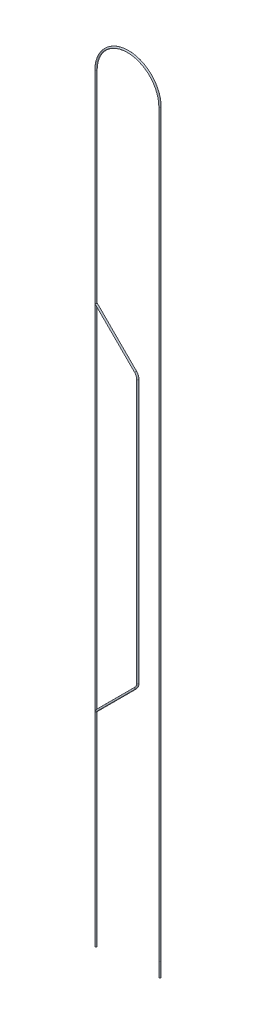
SolidWorks part; units mm, degrees
ref_plane "Plano frontal" through (0, 0, 0) normal (0, 0, 1) x (1, 0, 0)
ref_plane "Plano superior" through (0, 0, 0) normal (0, 1, 0) x (1, 0, 0)
ref_plane "Plano direito" through (0, 0, 0) normal (1, 0, 0) x (0, 0, -1)
sketch3d "3DSketch2"
  line L0 (-21588.0788, -1707.0358, 40468.4738) -> (-21588.0788, -1707.0358, 40492.9638) construction
  line L1 (-21551.0788, -1707.0358, 40468.4738) -> (-21551.0788, -1707.0358, 40480.4738) construction
  line L2 (-21551.0788, -1707.0358, 40468.4738) -> (-21625.0788, -1707.0358, 40468.4738) construction
  line L3 (-21625.0788, -1707.0358, 40468.4738) -> (-21625.0788, -1707.0358, 40480.4738) construction
  line L4 (-21551.0788, -1707.0358, 40480.4738) -> (-21625.0788, -1707.0358, 40480.4738) construction
  line L5 (-21588.0788, -1707.0358, 40492.9638) -> (-21588.0788, -1687.1987, 40492.9638) construction
  line L6 (-21588.0788, -1687.1987, 40492.9638) -> (-21618.6093, -1687.1987, 40492.9638) construction
  line L7 (-21588.0788, -1707.0358, 40492.9638) -> (-21588.0788, 11679.1105, 40492.9638)
  line L8 (-21588.0788, 11679.1105, 40492.9638) -> (-22746.0788, 11679.1105, 40492.9638) construction
  line L9 (-22746.0788, 11679.1105, 40492.9638) -> (-22746.0788, -1710.0519, 40492.9638)
  line L10 (-22167.0788, 11679.1105, 40492.9638) -> (-22167.0788, 12258.1105, 40492.9638) construction
  line L11 (-22746.0788, -1710.0519, 40492.9638) -> (-22746.0788, -2059.4505, 40492.9638)
  line L12 (-21588.0788, -1707.0358, 40492.9638) -> (-21588.0788, -1963.807, 40492.9638)
  line L13 (-22746.0788, -1710.0519, 40492.9638) -> (-21588.0788, -1710.0519, 40492.9638) construction
  circle A0 centre (-21588.0788, -1707.0358, 40492.9638) radius 16 construction
  arc A1 (-21578.0788, -1707.0358, 40480.4738) -> (-21598.0788, -1707.0358, 40480.4738) centre (-21588.0788, -1707.0358, 40492.9638) ccw construction
  circle A2 centre (-22746.0788, -1710.0519, 40492.9638) radius 16 construction
  arc A3 (-22736.0788, -1710.0519, 40480.4738) -> (-22756.0788, -1710.0519, 40480.4738) centre (-22746.0788, -1710.0519, 40492.9638) ccw construction
  arc A4 (-21588.0788, 11679.1105, 40492.9638) -> (-22746.0788, 11679.1105, 40492.9638) centre (-22167.0788, 11679.1105, 40492.9638) cw
  point P9 (-21588.0788, -1691.0358, 40492.9638)
  point P13 (-21588.0788, -1691.0358, 40492.9638)
  point P19 (-22746.0788, -1694.0519, 40492.9638)
  point P23 (-22746.0788, -1694.0519, 40492.9638)
  point P28 (-22167.0788, 11679.1105, 41071.9638)
sweep "Sweep-Thin1" add path "3DSketch2" circular profile diameter 30 parameters "D1"=2, "D3"=30
sketch3d "3DSketch3"
  line L0 (-22746.0788, -2059.4505, 40492.9638) -> (-22746.0788, 11140.5495, 40492.9638) construction
  line L1 (-22746.0788, 11679.1105, 40492.9638) -> (-22746.0788, -2059.4505, 40492.9638) construction
  line L2 (-22746.0788, 7266.2283, 40492.9638) -> (-21989.2814, 7266.2283, 40492.9638) construction
  line L3 (-21989.2814, 7266.2283, 40492.9638) -> (-21989.2814, 2389.4858, 40492.9638) construction
  line L4 (-21989.2814, 2389.4858, 40492.9638) -> (-22746.0788, 2389.4858, 40492.9638) construction
  line L5 (-22746.0788, 8023.0257, 40492.9638) -> (-22029.382, 7306.3289, 40492.9638)
  line L6 (-21989.2814, 7209.5176, 40492.9638) -> (-21989.2814, 2446.1965, 40492.9638)
  line L7 (-22029.382, 2349.3852, 40492.9638) -> (-22746.0788, 1632.6884, 40492.9638)
  line L8 (-22850.0788, -2672.1429, 40200.7738) -> (-22850.0788, 12327.8571, 40200.7738) construction
  line L9 (-22799.0788, -2672.1429, 40200.7738) -> (-22901.0788, -2672.1429, 40200.7738) construction
  line L10 (-22901.0788, 12327.8571, 40200.7738) -> (-22799.0788, 12327.8571, 40200.7738) construction
  line L11 (-22850.0788, 4827.8571, 40200.7738) -> (-21989.2814, 4827.8571, 40200.7738) construction
  line L12 (-21989.2814, 4827.8571, 40200.7738) -> (-21989.2814, 4827.8571, 40492.9638) construction
  arc A0 (-21989.2814, 2446.1965, 40492.9638) -> (-22029.382, 2349.3852, 40492.9638) centre (-22126.1933, 2446.1965, 40492.9638) ccw
  arc A1 (-22029.382, 7306.3289, 40492.9638) -> (-21989.2814, 7209.5176, 40492.9638) centre (-22126.1933, 7209.5176, 40492.9638) ccw
  point P12 (0, 0, 0)
  point P15 (-21989.2814, 2389.4858, 40492.9638)
  point P17 (-22126.1933, 2446.1965, 40356.052)
  point P20 (-21989.2814, 7266.2283, 40492.9638)
  point P22 (-22126.1933, 7209.5176, 40356.052)
  dimension "D3" = 136.9118
  dimension "D1" = 45
  dimension "D2" = 45
sweep "Sweep-Thin2" add path "3DSketch3" circular profile diameter 30 parameters "D1"=2, "D3"=30
